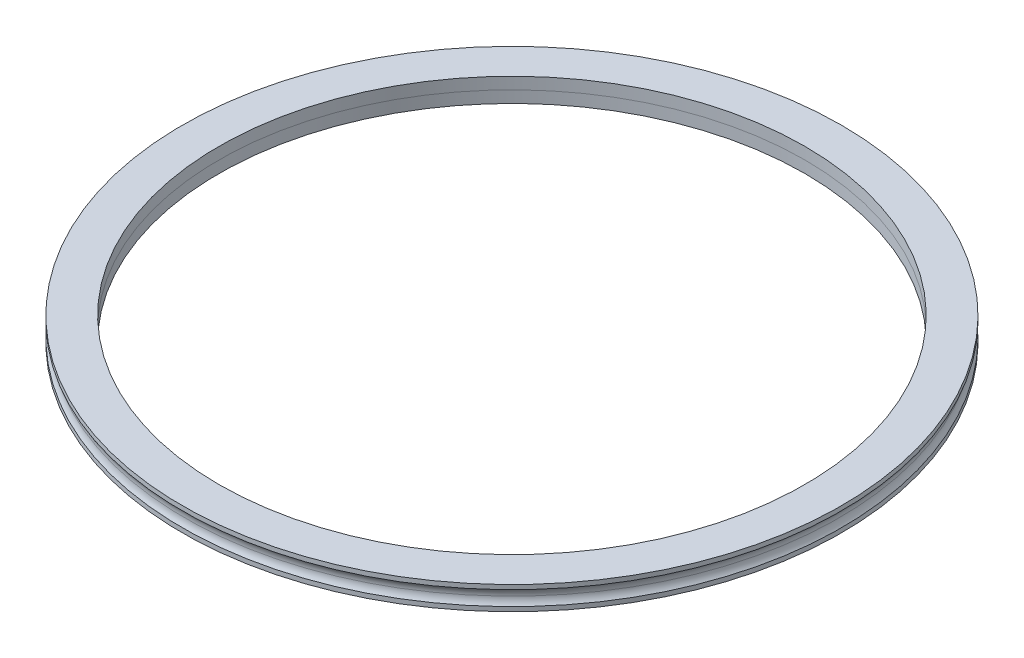
SolidWorks part; units mm, degrees
material "AISI 4340 Steel, normalized"
ref_plane "Front Plane" through (0, 0, 0) normal (0, 0, 1) x (1, 0, 0)
ref_plane "Top Plane" through (0, 0, 0) normal (0, 1, 0) x (1, 0, 0)
ref_plane "Right Plane" through (0, 0, 0) normal (1, 0, 0) x (0, 0, -1)
sketch "Sketch1" plane through (0, 0, 0) normal (0, 0, 1) x (1, 0, 0)
  line L1 (-60, 8.1325) -> (-60, 12.9625) construction
  line L2 (-60, 8.1325) -> (-67.5, 8.1325) construction
  line L3 (-67.5, 8.1325) -> (-67.5, 9.0475) construction
  line L4 (-67.5, 12.0475) -> (-67.5, 12.9625)
  line L5 (-60, 8.1325) -> (-60, 12.9625)
  line L6 (-60, 8.1325) -> (-67.5, 8.1325)
  line L7 (-67.5, 8.1325) -> (-67.5, 9.0475)
  line L8 (-60, 12.9625) -> (-67.5, 12.9625)
  line L10 (0, -200069.0475) -> (0, 200086.9028) construction
  line L11 (0, -200069.0475) -> (0, 200086.9028) construction
  arc A0 (-67.5, 9.0475) -> (-67.5, 12.0475) centre (-69.5, 10.5475) ccw construction
  arc A1 (-67.5, 9.0475) -> (-67.5, 12.0475) centre (-69.5, 10.5475) ccw
  point P9 (-67.5, 12.9625)
revolve "Revolve1" add sketch "Sketch1" angle 360 about L11
ref_plane "Midplane" through (0, 10.5475, 0) normal (0, 1, 0) x (1, 0, 0)
split "Split1" trim tools "Midplane" bodies to split 101 resulting bodies 102 103
